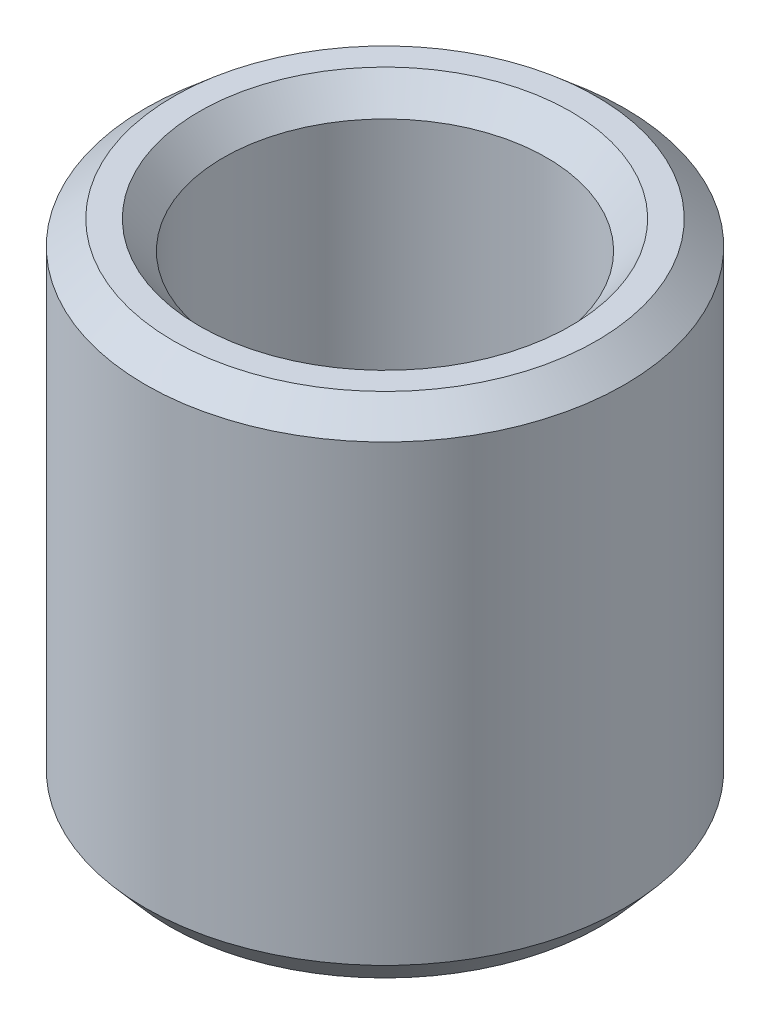
SolidWorks part; units mm, degrees
ref_plane "Front Plane" through (0, 0, 0) normal (0, 0, 1) x (1, 0, 0)
ref_plane "Top Plane" through (0, 0, 0) normal (0, 1, 0) x (1, 0, 0)
ref_plane "Right Plane" through (0, 0, 0) normal (1, 0, 0) x (0, 0, -1)
sketch "Sketch1" plane through (0, 0, 0) normal (0, 1, 0) x (1, 0, 0)
  circle A0 centre (0, 0) radius 22.5
  dimension "SLEEVE_OD" = 45
extrude "Boss-Extrude1" add sketch "Sketch1" along normal blind 47.4584
sketch "Sketch2" plane through (0, 0, 0) normal (0, 1, 0) x (1, 0, 0)
  circle A0 centre (0, 0) radius 15.1871
  dimension "BORE_D" = 30.3742
extrude "Cut-Extrude1" cut sketch "Sketch2" along normal through all
chamfer "Chamfer1" distance 2.2604 angle 49.239 4 edges at (0, 47.4584, 15.1871) (0, 0, 15.1871) (0, 0, 22.5) (0, 47.4584, 22.5) first distance on face at (0, 47.4584, 15.1871) first distance on face at (0, 0, 15.1871) first distance on face at (0, 47.4584, 22.5)
